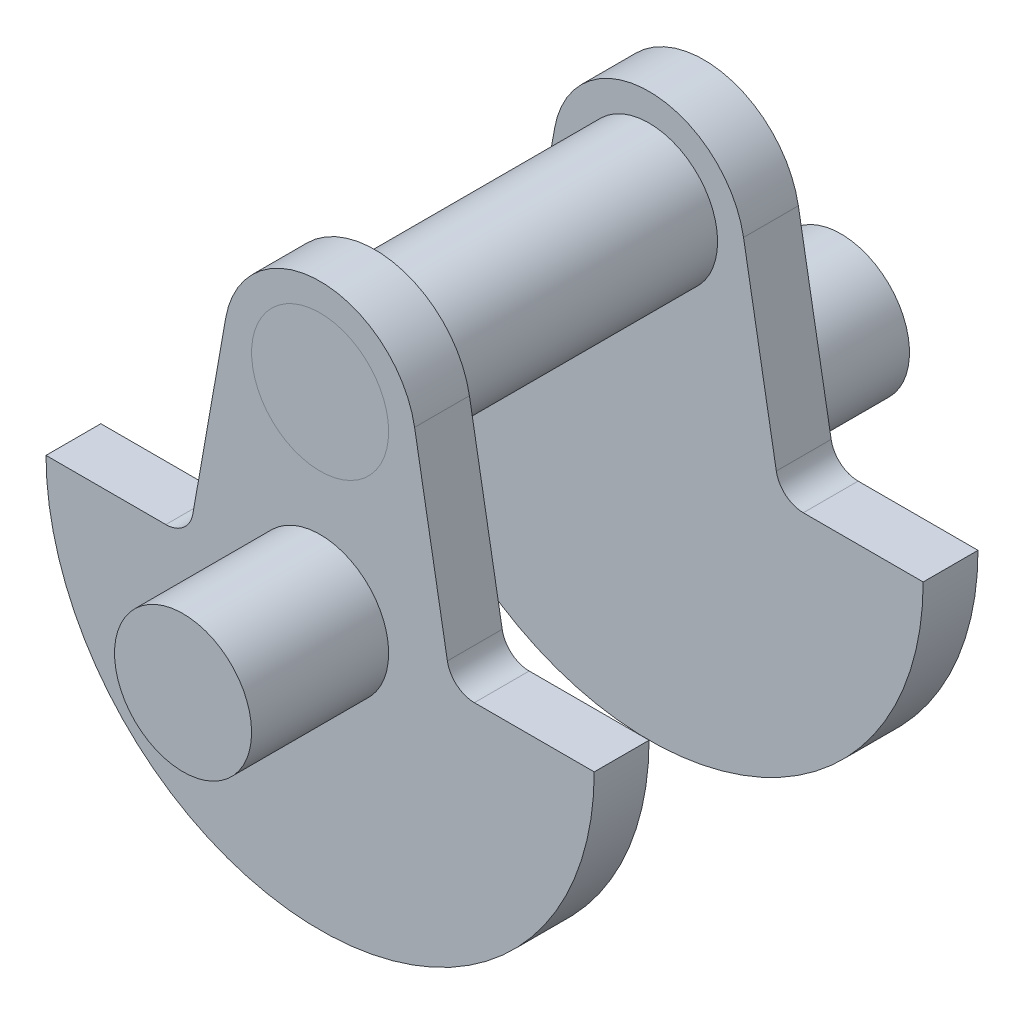
SolidWorks part; units mm, degrees
ref_plane "Front Plane" through (0, 0, 0) normal (0, 0, 1) x (1, 0, 0)
ref_plane "Top Plane" through (0, 0, 0) normal (0, 1, 0) x (1, 0, 0)
ref_plane "Right Plane" through (0, 0, 0) normal (1, 0, 0) x (0, 0, -1)
sketch "Sketch1" plane through (0, 0, 0) normal (0, 0, 1) x (1, 0, 0)
  line L0 (0, 0) -> (-64252.0609, 0) construction
  line L1 (0, 0) -> (0, 64252.0609) construction
  line L2 (-50, 0) -> (-28.1369, 0)
  line L3 (-23.2129, 4.1318) -> (-17.2341, 38.0388)
  line L4 (50, 0) -> (28.1369, 0)
  line L5 (23.2129, 4.1318) -> (17.2341, 38.0388)
  circle A0 centre (0, 0) radius 12.5
  arc A1 (-50, 0) -> (50, 0) centre (0, 0) ccw
  circle A2 centre (0, 35) radius 12.5
  arc A3 (17.2341, 38.0388) -> (-17.2341, 38.0388) centre (0, 35) ccw
  arc A4 (28.1369, 0) -> (23.2129, 4.1318) centre (28.1369, 5) cw
  arc A5 (-28.1369, 0) -> (-23.2129, 4.1318) centre (-28.1369, 5) ccw
  point P3 (33.7024, 72.9368)
  point P6 (0, 53.3595)
  point P16 (34.6161, 62.8632)
  point P18 (0, 0)
  point P21 (23.9414, 0)
  point P24 (-23.9414, 0)
  dimension "D1" = 25
  dimension "D2" = 17.5
  dimension "D3" = 25
  dimension "D6" = 50
  dimension "D8" = 5
  dimension "D4" = 10
  dimension "D5" = 10
  dimension "D7" = 35
extrude "Boss-Extrude1" add sketch "Sketch1" along normal blind 10
extrude "Boss-Extrude2" add sketch "Sketch1<2>" against normal blind 50 and the other way blind 10 separate body contours A2 region at (0, 35, 0)
sketch "Sketch1<2>" plane through (0, 0, 0) normal (0, 0, 1) x (1, 0, 0) same geometry as "Sketch1"
extrude "Boss-Extrude3" add sketch "Sketch1<3>" along normal blind 35 contours A0 region at (0, 0, 0)
sketch "Sketch1<3>" plane through (0, 0, 0) normal (0, 0, 1) x (1, 0, 0) same geometry as "Sketch1"
ref_plane "Plane1" through (0, 0, -50) normal (0, 0, -1) x (-1, 0, 0)
sketch "Sketch3" plane through (0, 0, -50) normal (0, 0, -1) x (-1, 0, 0)
  line L4 (50, 0) -> (28.1369, 0)
  line L5 (-28.1369, 0) -> (-50, 0)
  line L6 (-17.2341, 38.0388) -> (-23.2129, 4.1318)
  line L7 (23.2129, 4.1318) -> (17.2341, 38.0388)
  line L8 (50, 0) -> (28.1369, 0)
  line L9 (-28.1369, 0) -> (-50, 0)
  line L10 (-17.2341, 38.0388) -> (-23.2129, 4.1318)
  line L11 (23.2129, 4.1318) -> (17.2341, 38.0388)
  circle A1 centre (0, 35) radius 12.5
  circle A2 centre (0, 35) radius 12.5
  circle A3 centre (0, 0) radius 12.5
  circle A4 centre (0, 0) radius 12.5
  arc A8 (-50, 0) -> (50, 0) centre (0, 0) ccw
  arc A9 (-28.1369, 0) -> (-23.2129, 4.1318) centre (-28.1369, 5) ccw
  arc A10 (17.2341, 38.0388) -> (-17.2341, 38.0388) centre (0, 35) ccw
  arc A11 (23.2129, 4.1318) -> (28.1369, 0) centre (28.1369, 5) ccw
  arc A12 (-50, 0) -> (50, 0) centre (0, 0) ccw
  arc A13 (-28.1369, 0) -> (-23.2129, 4.1318) centre (-28.1369, 5) ccw
  arc A14 (17.2341, 38.0388) -> (-17.2341, 38.0388) centre (0, 35) ccw
  arc A15 (23.2129, 4.1318) -> (28.1369, 0) centre (28.1369, 5) ccw
  point P8 (0, 0)
  dimension "D1" = 0
  dimension "D2" = 0
  dimension "D3" = 0
extrude "Boss-Extrude4" add sketch "Sketch3" along normal blind 10 contours A15 L11 A14 L10 A13 L9 A12 L8 A4 A2 | A2 region at (0, -48.568, -50) region at (0, 35, -50)
extrude "Boss-Extrude5" add sketch "Sketch3<3>" along normal blind 35 contours A4 region at (0, 0, -50)
sketch "Sketch3<3>" plane through (0, 0, -50) normal (0, 0, -1) x (-1, 0, 0) same geometry as "Sketch3"
